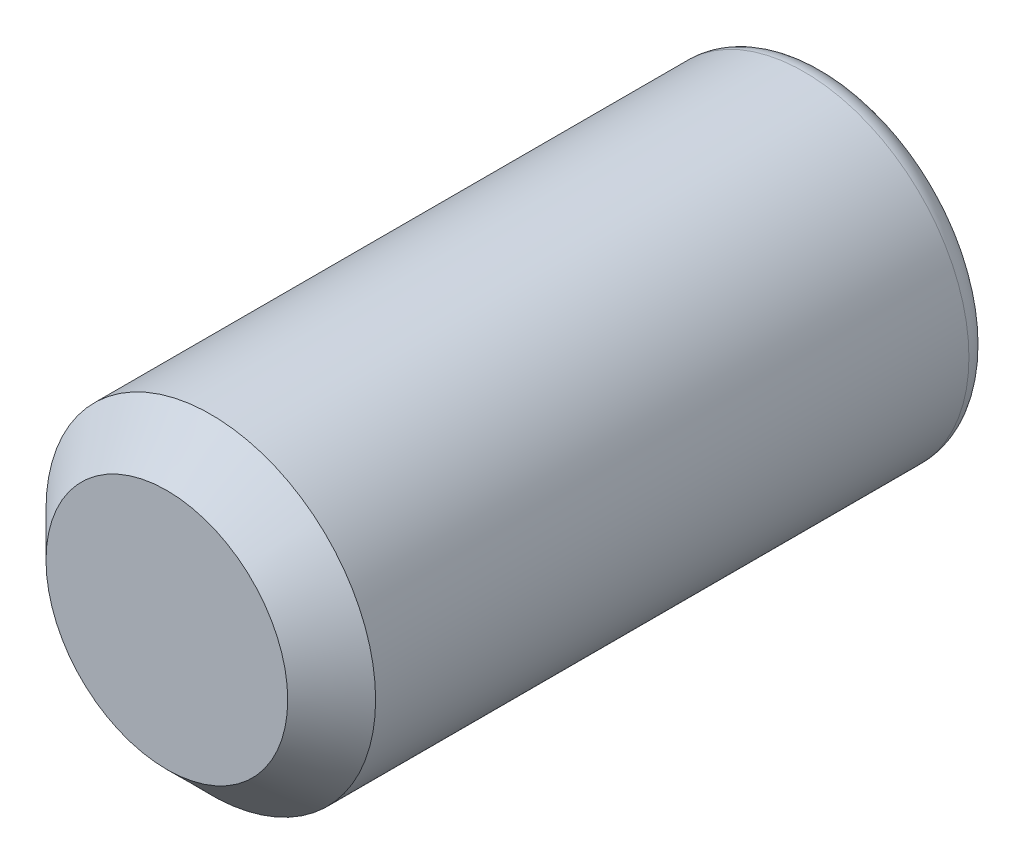
SolidWorks part; units mm, degrees
ref_plane "Front Plane" through (0, 0, 0) normal (0, 0, 1) x (1, 0, 0)
ref_plane "Top Plane" through (0, 0, 0) normal (0, 1, 0) x (1, 0, 0)
ref_plane "Right Plane" through (0, 0, 0) normal (1, 0, 0) x (0, 0, -1)
sketch "Sketch1" plane through (0, 0, 0) normal (0, 0, 1) x (1, 0, 0)
  circle A0 centre (0, 0) radius 1.5
  dimension "D1" = 3
extrude "Boss-Extrude1" add sketch "Sketch1" along normal blind 6
chamfer "Chamfer1" distance 0.4 angle 45 1 edges at (1.5, 0, 6)
fillet "Fillet1" radius 0.2 1 edges at (1.5, 0, 0)
sketch "Sketch2" plane through (0, 0, 0) normal (0, 0, -1) x (-1, 0, 0)
  line L1 (0, 0.866) -> (-0.75, 0.433)
  line L2 (-0.75, 0.433) -> (-0.75, -0.433)
  line L3 (-0.75, -0.433) -> (0, -0.866)
  line L4 (0, -0.866) -> (0.75, -0.433)
  line L5 (0.75, -0.433) -> (0.75, 0.433)
  line L6 (0.75, 0.433) -> (0, 0.866)
  circle A0 centre (0, 0) radius 0.75 construction
  dimension "D1" = 1.5
extrude "Cut-Extrude1" cut sketch "Sketch2" against normal blind 2
sketch "Sketch3" plane through (0, 0, 0) normal (0, 0, -1) x (-1, 0, 0)
  circle A0 centre (0, 0) radius 0.866
extrude "Cut-Extrude2" cut sketch "Sketch3" against normal blind 1 draft 45
